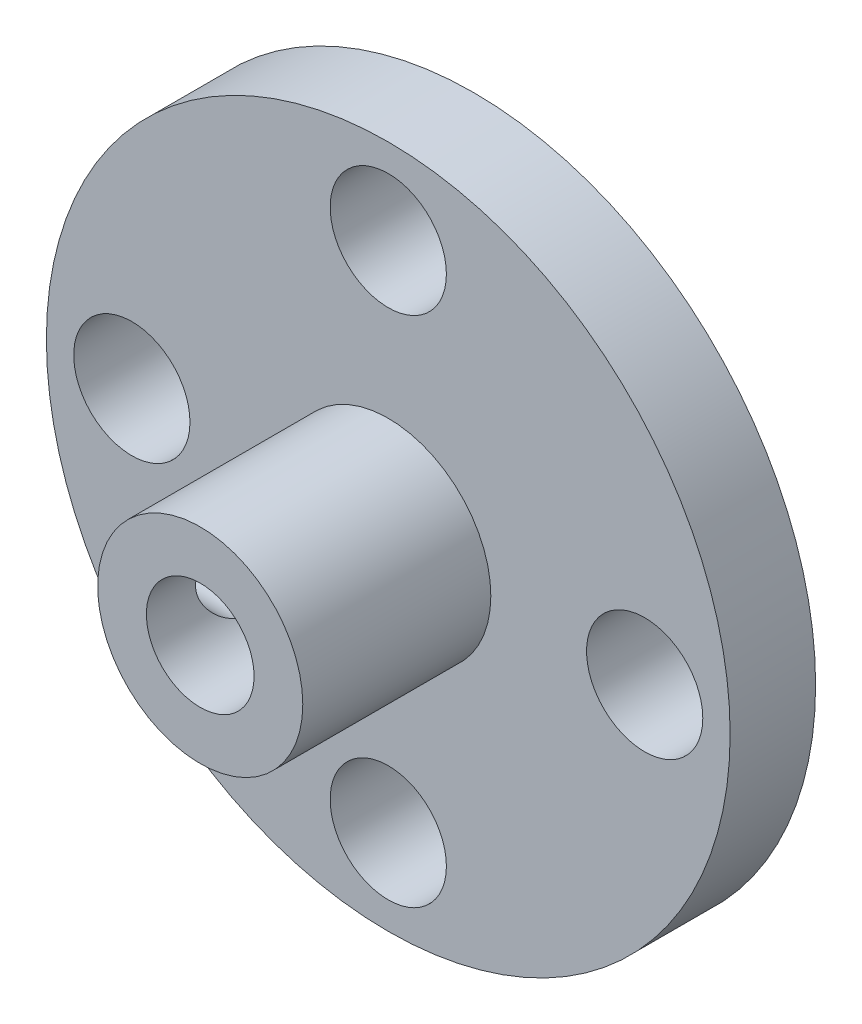
SolidWorks part; units mm, degrees
note: The reader was unsure of these and kept them because the rebuilt part matched: shared geometry of "Sketch2<3>".
ref_plane "Front Plane" through (0, 0, 0) normal (0, 0, 1) x (1, 0, 0)
ref_plane "Top Plane" through (0, 0, 0) normal (0, 1, 0) x (1, 0, 0)
ref_plane "Right Plane" through (0, 0, 0) normal (1, 0, 0) x (0, 0, -1)
sketch "Sketch2" plane through (0, 0, 0) normal (0, 0, 1) x (1, 0, 0)
  circle A0 centre (0, 0) radius 12.7
  circle A1 centre (0, 0) radius 2
  circle A2 centre (0, 0) radius 3.81
  circle A3 centre (0, 0) radius 9.525 construction
  circle A4 centre (0, 9.525) radius 2.159
  circle A5 centre (9.525, 0) radius 2.159
  circle A6 centre (0, -9.525) radius 2.159
  circle A7 centre (-9.525, 0) radius 2.159
  point P17 (0, 0)
  dimension "D1" = 4
  dimension "D2" = 25.4
  dimension "D3" = 7.62
  dimension "D4" = 19.05
  dimension "D5" = 4.318
  dimension "D6" = 4
extrude "Boss-Extrude1" add sketch "Sketch2" along normal blind 3.175 contours A2 A1 | A0 A7 A6 A5 A4 A2
extrude "Boss-Extrude2" add sketch "Sketch2<3>" along normal blind 10.16 contours A2 A1
sketch "Sketch2<3>" plane through (0, 0, 0) normal (0, 0, 1) x (1, 0, 0) same geometry as "Sketch2"
sketch "Sketch4" plane through (0, 0, 0) normal (1, 0, 0) x (0, 0, -1)
  line L0 (55, 0) -> (-55, 0) construction
  line L1 (-3.175, 12.7) -> (-3.175, -12.7) construction
  circle A0 centre (-6.985, 0) radius 1.35
  dimension "D1" = 2.7
  dimension "D2" = 3.81
extrude "Cut-Extrude1" cut sketch "Sketch4" against normal blind 12.7
